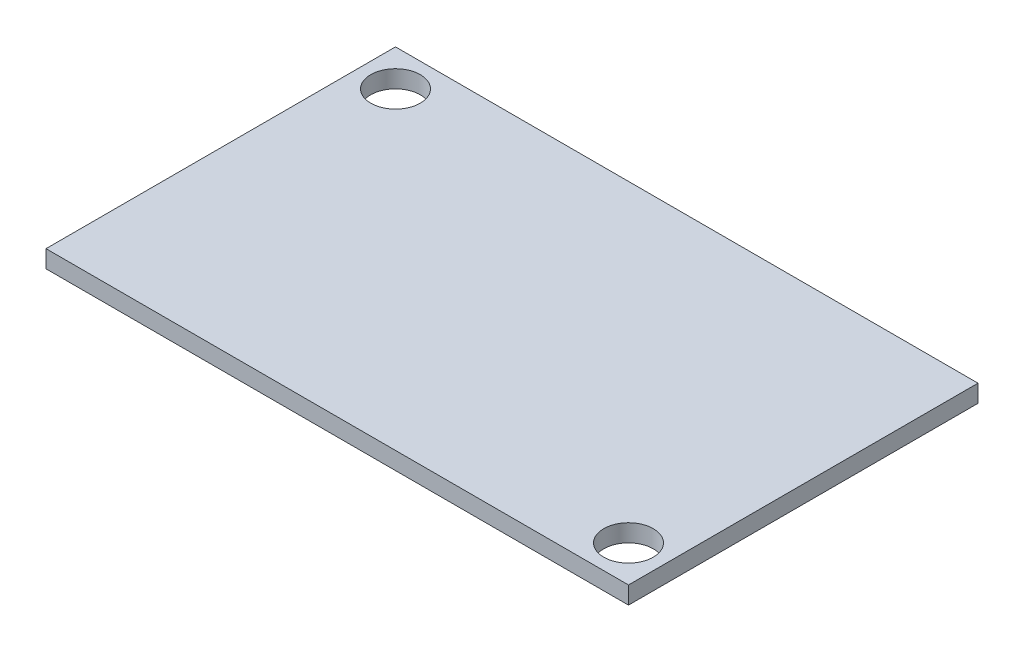
SolidWorks part; units mm, degrees
ref_plane "Front Plane" through (0, 0, 0) normal (0, 0, 1) x (1, 0, 0)
ref_plane "Top Plane" through (0, 0, 0) normal (0, 1, 0) x (1, 0, 0)
ref_plane "Right Plane" through (0, 0, 0) normal (1, 0, 0) x (0, 0, -1)
sketch "Sketch1" plane through (0, 0, 0) normal (0, 1, 0) x (1, 0, 0)
  line L1 (-24.7775, 1.3586) -> (15.2225, 1.3586)
  line L2 (-24.7775, 1.3586) -> (-24.7775, -22.6414)
  line L3 (-24.7775, -22.6414) -> (15.2225, -22.6414)
  line L4 (15.2225, 1.3586) -> (15.2225, -22.6414)
  dimension "D1" = 24
  dimension "D2" = 40
extrude "Boss-Extrude1" add sketch "Sketch1" along normal blind 1.2
hole_wizard "M3 Clearance Hole1" positions "3DSketch1" profile "Sketch2" hole size "M3" standard "ANSI Metric" end condition through all
sketch3d "3DSketch1"
  line L0 (-24.7775, 1.2, 22.6414) -> (15.2225, 1.2, 22.6414) construction
  line L1 (15.2225, 1.2, 22.6414) -> (15.2225, 1.2, -1.3586) construction
  line L2 (-24.7775, 1.2, -1.3586) -> (-24.7775, 1.2, 22.6414) construction
  line L3 (15.2225, 1.2, -1.3586) -> (-24.7775, 1.2, -1.3586) construction
  point P0 (-22.2775, 1.2, 1.1414)
  point P2 (12.7225, 1.2, 20.1414)
  dimension "D1" = 2.5
  dimension "D2" = 2.5
  dimension "D3" = 2.5
  dimension "D4" = 2.5
sketch "Sketch2" plane through (-22.2775, 1.2, 1.1414) normal (1, 0, 0) x (0, 0, 1)
  line L0 (0, 0) -> (0, 1.2)
  line L1 (0, 1.2) -> (1.7, 1.2)
  line L2 (1.7, 1.2) -> (1.7, 0)
  line L5 (1.7, 0) -> (0, 0)
  line L11 (0, -6.35) -> (0, 107.95) construction
  dimension "Thru Hole Dia." = 3.4
  dimension "Thru Hole Depth" = 1.2
